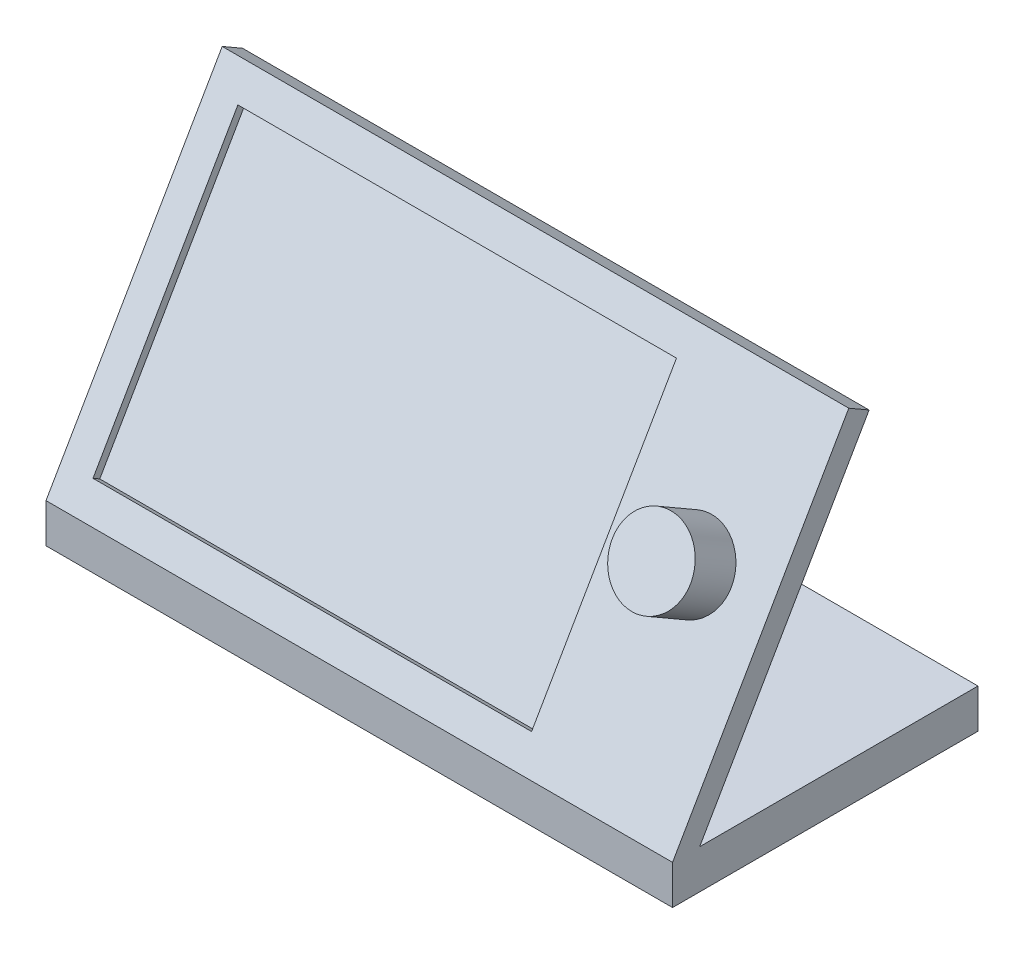
SolidWorks part; units mm, degrees
ref_plane "Front Plane" through (0, 0, 0) normal (0, 0, 1) x (1, 0, 0)
ref_plane "Top Plane" through (0, 0, 0) normal (0, 1, 0) x (1, 0, 0)
ref_plane "Right Plane" through (0, 0, 0) normal (1, 0, 0) x (0, 0, -1)
sketch "Sketch1" plane through (0, 0, 0) normal (0, 0, 1) x (1, 0, 0)
  line L1 (0, 0) -> (-101.6, 0)
  line L2 (0, 0) -> (0, 6.35)
  line L3 (0, 6.35) -> (-101.6, 6.35)
  line L4 (-101.6, 0) -> (-101.6, 6.35)
  dimension "D1" = 6.35
  dimension "D2" = 101.6
extrude "Boss-Extrude1" add sketch "Sketch1" along normal blind 25.4 and the other way blind 24.13
sketch "Sketch2" plane through (0, 0, 0) normal (1, 0, 0) x (0, 0, -1)
  line L0 (-25.4, 6.35) -> (3.175, 55.8434)
  line L1 (-25.4, 6.35) -> (24.13, 6.35) construction
  line L2 (3.175, 55.8434) -> (6.4746, 53.9384)
  line L3 (6.4746, 53.9384) -> (-21.0006, 6.35)
  line L4 (-25.4, 6.35) -> (-21.0006, 6.35)
  dimension "D1" = 60
  dimension "D2" = 57.15
  dimension "D3" = 3.81
extrude "Boss-Extrude2" add sketch "Sketch2" against normal up to surface (101.6 mm away) up to face at (-101.6, 3.175, 0.635)
sketch "Sketch3" plane through (0, 12.586, 21.7996) normal (0, 0.5, 0.866) x (1, 0, 0)
  line L0 (-101.6, -7.2007) -> (-101.6, 49.9493) construction
  line L1 (-96.52, 44.8693) -> (-25.4, 44.8693)
  line L2 (-96.52, 44.8693) -> (-96.52, -2.1207)
  line L3 (-96.52, -2.1207) -> (-25.4, -2.1207)
  line L4 (-25.4, 44.8693) -> (-25.4, -2.1207)
  line L5 (-101.6, 49.9493) -> (0, 49.9493) construction
  line L6 (0, -7.2007) -> (-101.6, -7.2007) construction
  line L7 (0, 49.9493) -> (0, -7.2007) construction
  dimension "D1" = 5.08
  dimension "D2" = 5.08
  dimension "D3" = 5.08
  dimension "D4" = 25.4
extrude "Cut-Extrude1" cut sketch "Sketch3" against normal blind 1.27
sketch "Sketch4" plane through (0, 12.586, 21.7996) normal (0, 0.5, 0.866) x (1, 0, 0)
  line L0 (0, 49.9493) -> (0, -7.2007) construction
  line L2 (-101.6, 49.9493) -> (0, 49.9493) construction
  circle A0 centre (-12.7, 24.5493) radius 6.35
  dimension "D1" = 12.7
  dimension "D2" = 12.7
  dimension "D3" = 25.4
extrude "Boss-Extrude3" add sketch "Sketch4" along normal blind 7.62
